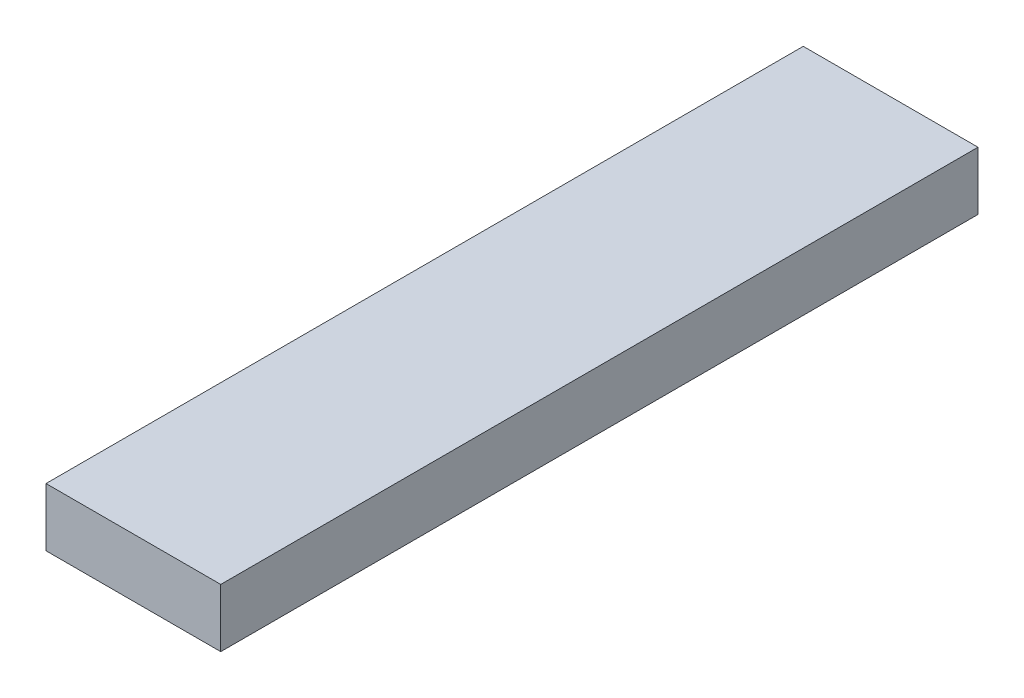
SolidWorks part; units mm, degrees
ref_plane "Front Plane" through (0, 0, 0) normal (0, 0, 1) x (1, 0, 0)
ref_plane "Top Plane" through (0, 0, 0) normal (0, 1, 0) x (1, 0, 0)
ref_plane "Right Plane" through (0, 0, 0) normal (1, 0, 0) x (0, 0, -1)
sketch "Sketch1" plane through (0, 0, 0) normal (0, 0, 1) x (1, 0, 0)
  line L1 (-45, -15) -> (45, -15)
  line L2 (-45, -15) -> (-45, 15)
  line L3 (-45, 15) -> (45, 15)
  line L4 (45, -15) -> (45, 15)
  line L5 (-45, -15) -> (45, 15) construction
  line L6 (-45, 15) -> (45, -15) construction
  point P0 (0, 0)
  dimension "D1" = 90
  dimension "D2" = 30
extrude "Boss-Extrude1" add sketch "Sketch1" along normal mid plane 390
